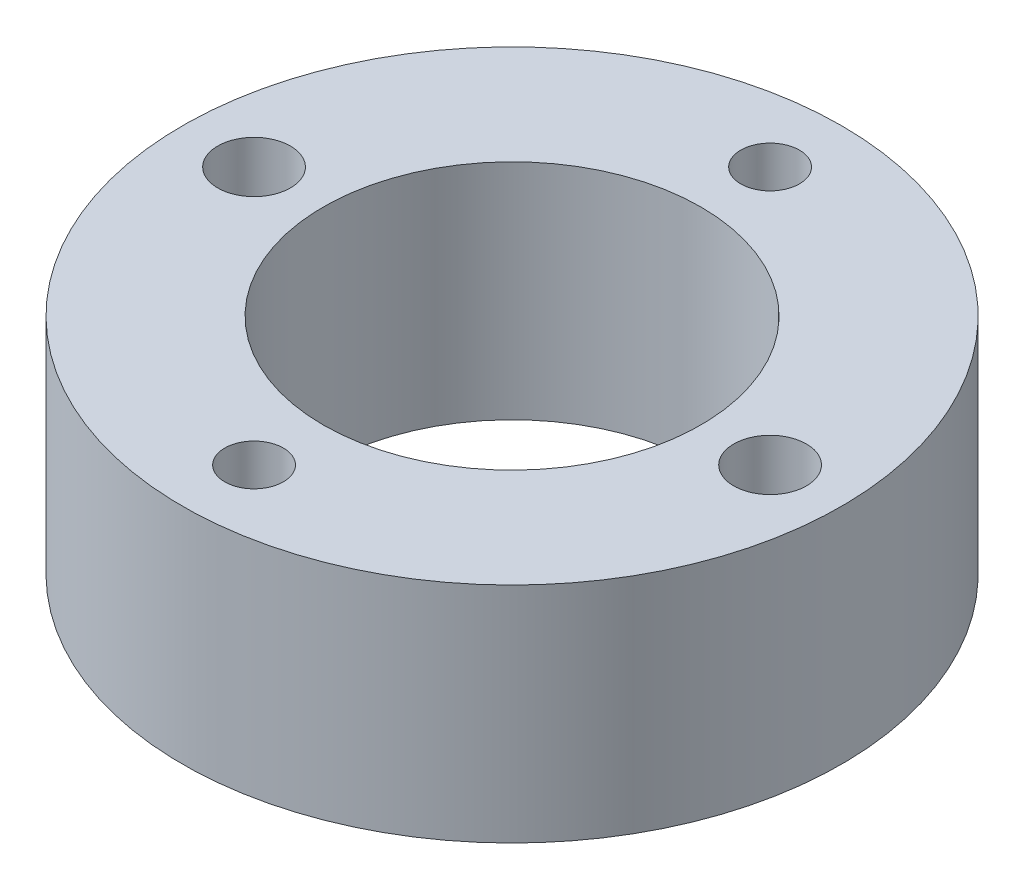
SolidWorks part; units mm, degrees
ref_plane "Front Plane" through (0, 0, 0) normal (0, 0, 1) x (1, 0, 0)
ref_plane "Top Plane" through (0, 0, 0) normal (0, 1, 0) x (1, 0, 0)
ref_plane "Right Plane" through (0, 0, 0) normal (1, 0, 0) x (0, 0, -1)
sketch "Sketch1" plane through (0, 0, 0) normal (0, 1, 0) x (1, 0, 0)
  circle A0 centre (0, 0) radius 8.05
  circle A1 centre (0, 0) radius 14.05
  circle A2 centre (0, 0) radius 11 construction
  circle A3 centre (11, 0) radius 1.55
  circle A4 centre (-11, 0) radius 1.55
  circle A5 centre (0, 11) radius 1.25
  circle A6 centre (0, -11) radius 1.25
  dimension "D1" = 16.1
  dimension "D2" = 6
  dimension "D3" = 22
  dimension "D4" = 3.1
  dimension "D5" = 2.5
extrude "Boss-Extrude1" add sketch "Sketch1" along normal blind 9.525
